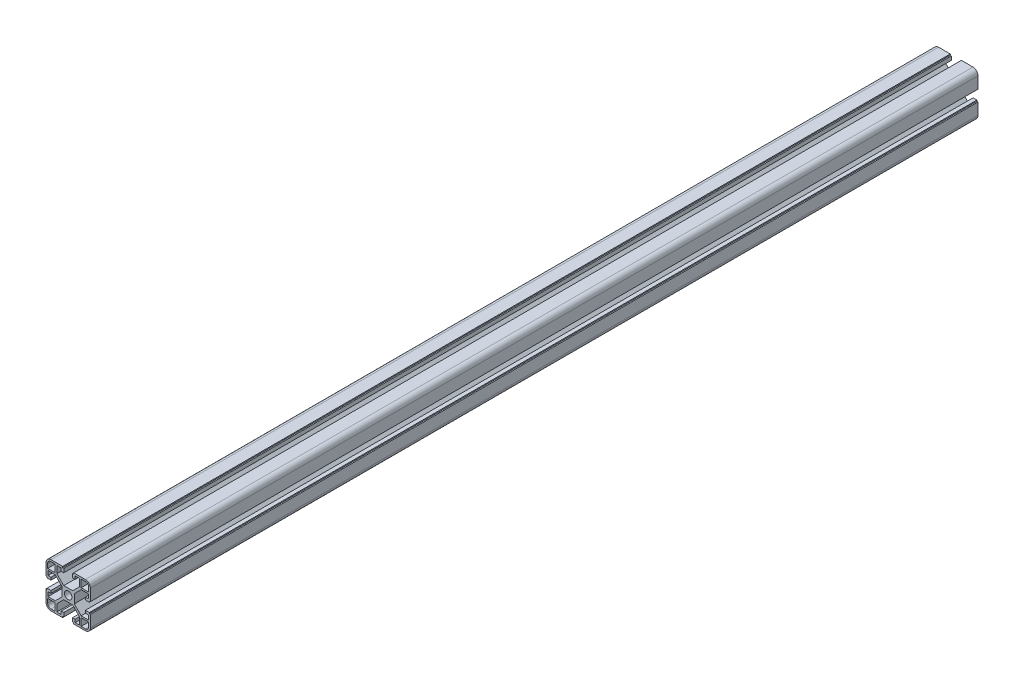
SolidWorks part; units mm, degrees
material "6061-T6 (SS)"
ref_plane "Front Plane" through (0, 0, 0) normal (0, 0, 1) x (1, 0, 0)
ref_plane "Top Plane" through (0, 0, 0) normal (0, 1, 0) x (1, 0, 0)
ref_plane "Right Plane" through (0, 0, 0) normal (1, 0, 0) x (0, 0, -1)
sketch "Sketch1" plane through (0, 0, 0) normal (0, 0, 1) x (1, 0, 0)
  line L0 (3.4, 0) -> (5.5, 0)
  line L1 (10.19, 11.69) -> (4, 5.5)
  line L2 (11.69, 10.19) -> (5.5, 4)
  line L3 (18.2, 10.19) -> (11.69, 10.19)
  line L4 (18.2, 10.19) -> (18.2, 6.3)
  line L5 (18.2, 6.3) -> (15.5, 6.3)
  line L6 (15.5, 6.3) -> (15.5, 4)
  line L7 (15.5, 4) -> (19, 4)
  line L8 (19, 4) -> (19, 5)
  line L9 (19, 5) -> (20, 5)
  line L10 (20, 5) -> (20, 15.5)
  line L11 (15.5, 20) -> (5, 20)
  line L12 (18.5, 11.69) -> (18.5, 15.5)
  line L13 (15.5, 18.5) -> (11.69, 18.5)
  line L14 (11.69, 11.69) -> (11.69, 18.5)
  line L15 (0, 3.4) -> (0, 5.5)
  line L16 (4, 5.5) -> (0, 5.5)
  line L17 (5, 20) -> (5, 19)
  line L18 (5.5, 0) -> (5.5, 4)
  line L19 (5, 19) -> (4, 19)
  line L20 (4, 19) -> (4, 15.5)
  line L21 (4, 15.5) -> (6.3, 15.5)
  line L22 (10.19, 11.69) -> (10.19, 18.2)
  line L23 (11.69, 11.69) -> (18.5, 11.69)
  line L24 (6.3, 18.2) -> (6.3, 15.5)
  line L25 (10.19, 18.2) -> (6.3, 18.2)
  arc A0 (20, 15.5) -> (15.5, 20) centre (15.5, 15.5) ccw
  arc A1 (18.5, 15.5) -> (15.5, 18.5) centre (15.5, 15.5) ccw
  arc A2 (3.4, 0) -> (0, 3.4) centre (0, 0) ccw
  point P4 (0, 4.45)
  dimension "D3" = 4.5
  dimension "D18" = 1.5
  dimension "D9" = 3.4
  dimension "D20" = 1.8
  dimension "D25" = 3
  dimension "D1" = 5.5
  dimension "D2" = 1.5
  dimension "D4" = 14.5
  dimension "D5" = 1.5
  dimension "D6" = 2.1
  dimension "D7" = 2.3
  dimension "D8" = 1.8
  dimension "D10" = 6.81
  dimension "D11" = 2.1
  dimension "D12" = 1
  dimension "D13" = 4.5
  dimension "D14" = 45
  dimension "D15" = 14.5
  dimension "D16" = 1
  dimension "D17" = 1.5
  dimension "D19" = 6.81
  dimension "D21" = 4.5
  dimension "D22" = 2.3
  dimension "D23" = 1
  dimension "D24" = 1
  dimension "D26" = 8.754
  dimension "D27" = 8.754
  dimension "D28" = 4
  dimension "D29" = 4
extrude "Boss-Extrude1" add sketch "Sketch1" along normal blind 800
mirror "Mirror1" about plane through (0, 0, 0) normal (0, 1, 0) of "Boss-Extrude1"
mirror "Mirror2" about plane through (0, 0, 0) normal (1, 0, 0) of "Boss-Extrude1"
mirror "Mirror3" about plane through (0, 0, 0) normal (0, 1, 0) of "Mirror2"
